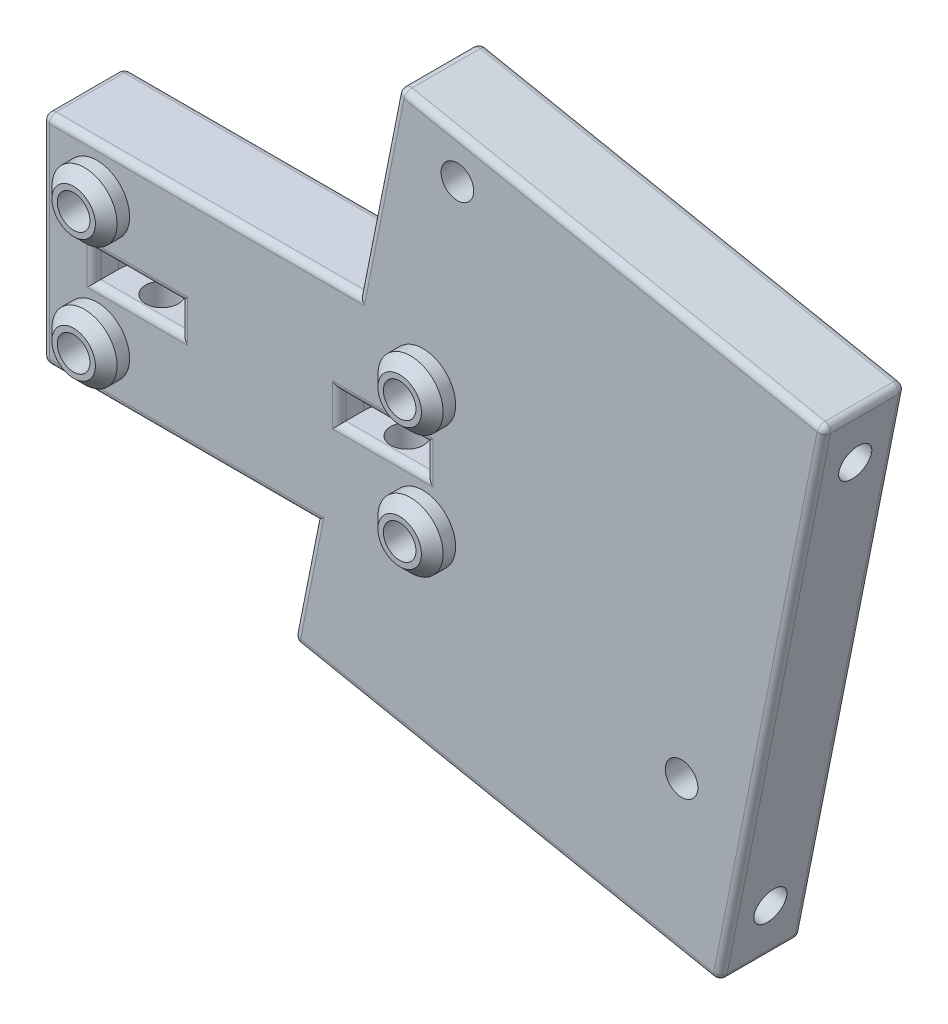
SolidWorks part; units mm, degrees
ref_plane "Front Plane" through (0, 0, 0) normal (0, 0, 1) x (1, 0, 0)
ref_plane "Top Plane" through (0, 0, 0) normal (0, 1, 0) x (1, 0, 0)
ref_plane "Right Plane" through (0, 0, 0) normal (1, 0, 0) x (0, 0, -1)
sketch "Sketch1" plane through (0, 0, 0) normal (0, 0, 1) x (1, 0, 0)
  line L2 (-38.1, -12.7) -> (-38.1, 12.7)
  line L3 (-38.1, 12.7) -> (38.1, 12.7)
  line L10 (38.1, -12.7) -> (38.1, 12.7)
  line L11 (-38.1, -12.7) -> (38.1, -12.7)
  line L14 (-38.1, 12.7) -> (38.1, -12.7) construction
  point P2 (0, 0)
  dimension "D1" = 76.2
  dimension "D2" = 25.4
extrude "Boss-Extrude1" add sketch "Sketch1" along normal blind 9.525
sketch "Sketch6" plane through (0, 0, 9.525) normal (0, 0, -1) x (-1, 0, 0)
  line L4 (8.8811, -26.1846) -> (-40.9428, -36.0952)
  line L6 (8.8811, -26.1846) -> (-3.5072, 36.0952)
  line L23 (-40.9428, -36.0952) -> (-53.3311, 26.1846)
  line L24 (-3.5072, 36.0952) -> (-53.3311, 26.1846)
  line L25 (8.8811, -26.1846) -> (-53.3311, 26.1846) construction
  line L26 (-40.9428, -36.0952) -> (-3.5072, 36.0952) construction
  line L27 (-38.1, 12.7) -> (38.1, 12.7) construction
  point P1 (-22.225, 0)
  dimension "D1" = 50.8
  dimension "D2" = 63.5
  dimension "D3" = 11.25
  dimension "D4" = 0
  dimension "D5" = 22.225
extrude "Boss-Extrude2" add sketch "Sketch6" along normal up to surface (9.525 mm away) up to face at (0, 0, 0)
sketch "Sketch4" plane through (0, 0, 0) normal (0, 1, 0) x (1, 0, 0)
  line L7 (-1.1464, -9.525) -> (-38.1, -9.525) construction
  line L8 (-32.0992, -6.6675) -> (-32.0992, -9.525)
  line L9 (-21.9392, -6.6675) -> (-21.9392, -9.525)
  line L10 (-21.9392, -9.525) -> (-32.0992, -9.525)
  line L11 (-38.1, -9.525) -> (-38.1, 0) construction
  arc A2 (-21.9392, -6.6675) -> (-32.0992, -6.6675) centre (-27.0192, -6.6675) ccw
  dimension "D1" = 10.16
  dimension "D2" = 2.8575
  dimension "D3" = 11.0808
extrude "Cut-Extrude2" cut sketch "Sketch4" against normal mid plane 3.302
ref_plane "Plane3" through (-12.7, 0, 0) normal (-1, 0, 0) x (0, 0, 1)
sketch "Sketch2" plane through (0, 0, 9.525) normal (0, 0, 1) x (1, 0, 0)
  line L1 (-38.1, 12.7) -> (-38.1, -12.7) construction
  line L2 (0, 0) -> (-38.1, 0) construction
  line L3 (-38.1, 12.7) -> (-38.1, -12.7) construction
  circle A0 centre (-31.75, 7.1755) radius 1.905
  circle A1 centre (-31.75, -7.1755) radius 1.905
  dimension "D1" = 3.81
  dimension "D2" = 14.351
  dimension "D3" = 6.35
extrude "Cut-Extrude1" cut sketch "Sketch2" against normal through all both and the other way through all
sketch "Sketch11" plane through (0, 0, 9.525) normal (0, 0, 1) x (1, 0, 0)
  circle A0 centre (-31.75, 7.1755) radius 3.81
  circle A1 centre (-31.75, 7.1755) radius 1.905
  circle A2 centre (-31.75, 7.1755) radius 1.905 construction
  circle A3 centre (-31.75, -7.1755) radius 3.81
  circle A4 centre (-31.75, -7.1755) radius 1.905
  dimension "D1" = 7.62
extrude "Boss-Extrude5" add sketch "Sketch11" along normal blind 2.7305
sketch "Sketch5" plane through (0, 12.7, 0) normal (0, 1, 0) x (1, 0, 0)
  line L0 (-1.1464, -9.525) -> (-38.1, -9.525) construction
  line L1 (-38.1, -9.525) -> (-38.1, 0) construction
  circle A0 centre (-27.0192, -6.6675) radius 1.905
  dimension "D3" = 3.81
  dimension "D1" = 2.8575
  dimension "D2" = 11.0808
extrude "Cut-Extrude3" cut sketch "Sketch5" against normal through all from offset 6.35 offset against normal yes
mirror "Mirror1" about plane through (-12.7, 0, 0) normal (-1, 0, 0) of "Cut-Extrude1", "Cut-Extrude3", "Cut-Extrude2", "Boss-Extrude5"
chamfer "Chamfer4" distance 1.27 angle 45 4 edges at (-27.94, -7.1755, 12.2555) (2.54, -7.1755, 12.2555) (2.54, 7.1755, 12.2555) (-27.94, 7.1755, 12.2555)
fillet "Fillet3" radius 0.7937 30 edges at (-38.1, 0, 9.525) (-38.1, -12.7, 4.7625) (-38.1, 0, 0) (-38.1, 12.7, 4.7625) (-19.6232, 12.7, 0) (-19.6232, 12.7, 9.525) (1.1804, 24.3976, 9.525) (1.1804, 24.3976, 0) (3.5072, 36.0952, 4.7625) (28.4191, 31.1399, 0) (28.4191, 31.1399, 9.525) (53.3311, 26.1846, 4.7625) (47.1369, -4.9553, 0) (47.1369, -4.9553, 9.525) (40.9428, -36.0952, 4.7625) (16.0309, -31.1399, 0) (16.0309, -31.1399, 9.525) (-8.8811, -26.1846, 4.7625) (-7.5399, -19.4423, 9.525) (-7.5399, -19.4423, 0) (-22.1494, -12.7, 0) (-22.1494, -12.7, 9.525) (1.6193, -1.651, 9.525) (6.6993, 0, 9.525) (1.6193, 1.651, 9.525) (-3.4607, 0, 9.525) (-21.9392, 0, 9.525) (-32.0992, 0, 9.525) (-27.0192, 1.651, 9.525) (-27.0192, -1.651, 9.525)
sketch "Sketch12" plane through (46.2911, -9.2079, 0) normal (0.9808, -0.1951, 0) x (0, 0, -1)
  circle A6 centre (-4.7625, -21.0641) radius 1.905
  circle A7 centre (-4.7625, 29.7359) radius 1.905
  dimension "D1" = 3.81
extrude "Cut-Extrude4" cut sketch "Sketch12" against normal blind 9.525
sketch "Sketch13" plane through (-3.5328, 0.7027, 0) normal (-0.9808, 0.1951, 0) x (0, 0, 1)
  circle A0 centre (4.7625, 29.7359) radius 1.905
  circle A1 centre (4.7625, -21.0641) radius 1.905
  dimension "D1" = 3.81
extrude "Cut-Extrude5" cut sketch "Sketch13" against normal blind 9.525
sketch "Sketch14" plane through (0, 0, 0) normal (0, 0, -1) x (-1, 0, 0)
  circle A0 centre (-10.363, 29.8757) radius 1.905
  circle A1 centre (-36.5646, -17.4197) radius 1.905
  circle A2 centre (-10.363, 29.8757) radius 2.286 construction
  circle A3 centre (-36.5646, -17.4197) radius 2.286 construction
  dimension "D1" = 3.81
extrude "Cut-Extrude6" cut sketch "Sketch14" against normal through all
